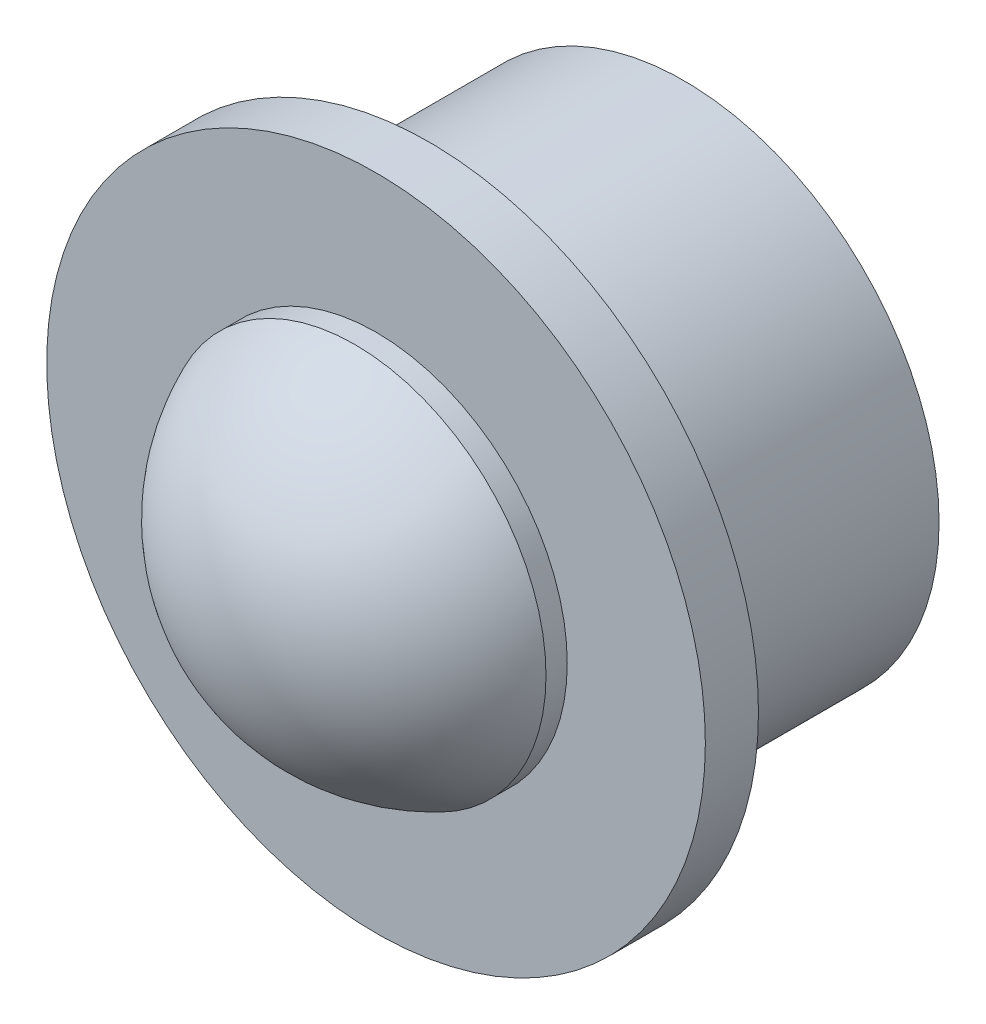
SolidWorks part; units mm, degrees
ref_plane "Plan de face" through (0, 0, 0) normal (0, 0, 1) x (1, 0, 0)
ref_plane "Plan de dessus" through (0, 0, 0) normal (0, 1, 0) x (1, 0, 0)
ref_plane "Plan de droite" through (0, 0, 0) normal (1, 0, 0) x (0, 0, -1)
sketch "Esquisse1" plane through (0, 0, 0) normal (0, 0, 1) x (1, 0, 0)
  circle A0 centre (0, 0) radius 12
extrude "Extrusion1" add sketch "Esquisse1" along normal blind 12
sketch "Esquisse2" plane through (0, 0, 12) normal (0, 0, 1) x (1, 0, 0)
  circle A0 centre (0, 0) radius 15.5
extrude "Extrusion2" add sketch "Esquisse2" along normal blind 2.5
sketch "Esquisse3" plane through (0, 0, 14.5) normal (0, 0, 1) x (1, 0, 0)
  circle A0 centre (0, 0) radius 9
extrude "Extrusion3" add sketch "Esquisse3" along normal blind 1
dome "Dôme1" faces to dome 1 distance 6 reverse direction no elliptical dome no face at (9, 0, 15.5) parameters "D1"=6
